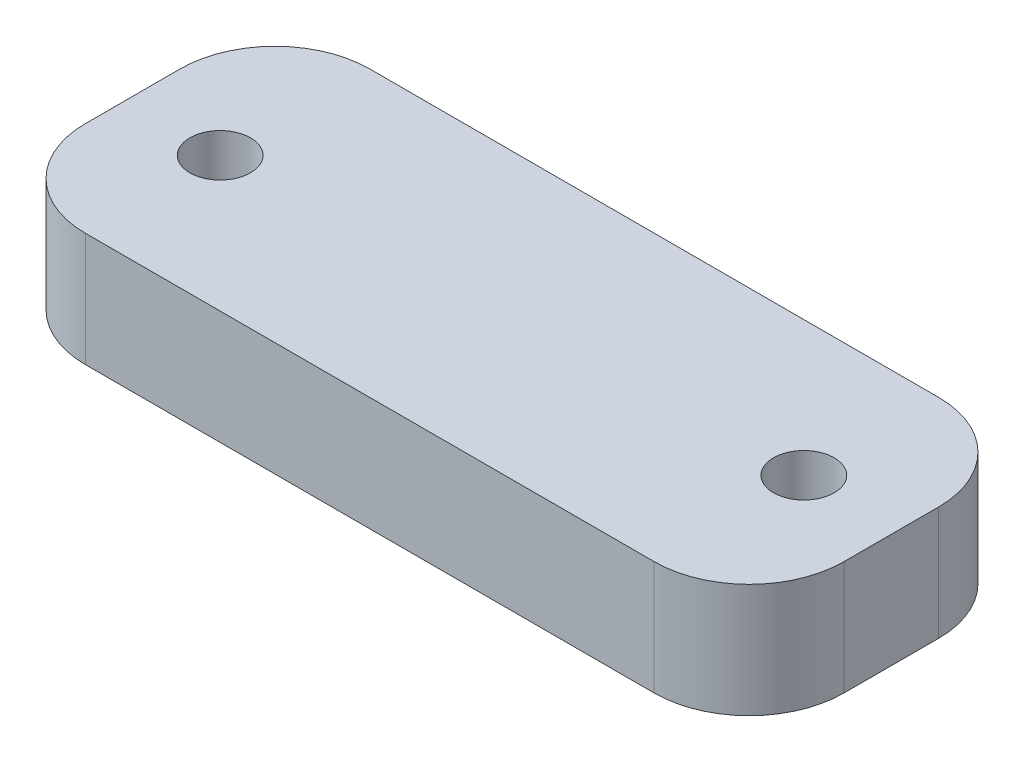
SolidWorks part; units mm, degrees
material "Maple"
ref_plane "Front Plane" through (0, 0, 0) normal (0, 0, 1) x (1, 0, 0)
ref_plane "Top Plane" through (0, 0, 0) normal (0, 1, 0) x (1, 0, 0)
ref_plane "Right Plane" through (0, 0, 0) normal (1, 0, 0) x (0, 0, -1)
sketch "Sketch1" plane through (0, 0, 0) normal (0, 1, 0) x (1, 0, 0)
  line L1 (-20, 7.5) -> (20, 7.5)
  line L2 (-20, 7.5) -> (-20, -7.5)
  line L3 (-20, -7.5) -> (20, -7.5)
  line L4 (20, 7.5) -> (20, -7.5)
  line L5 (-20, 7.5) -> (20, -7.5) construction
  line L6 (-20, -7.5) -> (20, 7.5) construction
  point P0 (0, 0)
  dimension "D1" = 40
  dimension "D2" = 15
extrude "Boss-Extrude1" add sketch "Sketch1" along normal blind 6
ref_plane "Plane1" through (0, 3, 0) normal (0, 1, 0) x (1, 0, 0)
hole_wizard "M3 Clearance Hole1" positions "Sketch3" profile "Sketch2" hole size "M3" standard "ANSI Metric" end condition through all
sketch "Sketch3" plane through (0, 6, 0) normal (0, 1, 0) x (1, 0, 0)
  line L0 (-15, -0.3886) -> (15, 0.3886) construction
  point P0 (-15, -0.3886)
  point P2 (15, 0.3886)
  dimension "D1" = 30
sketch "Sketch2" plane through (-15, 6, 0.3886) normal (1, 0, 0) x (0, 0, 1)
  line L0 (0, 0) -> (0, 6)
  line L1 (0, 6) -> (1.6, 6)
  line L2 (1.6, 6) -> (1.6, 0)
  line L5 (1.6, 0) -> (0, 0)
  line L11 (0, -6.35) -> (0, 107.95) construction
  dimension "Thru Hole Dia." = 3.2
  dimension "Thru Hole Depth" = 6
fillet "Fillet1" radius 5 4 edges at (20, 3, 7.5) (-20, 3, -7.5) (20, 3, -7.5) (-20, 3, 7.5)
